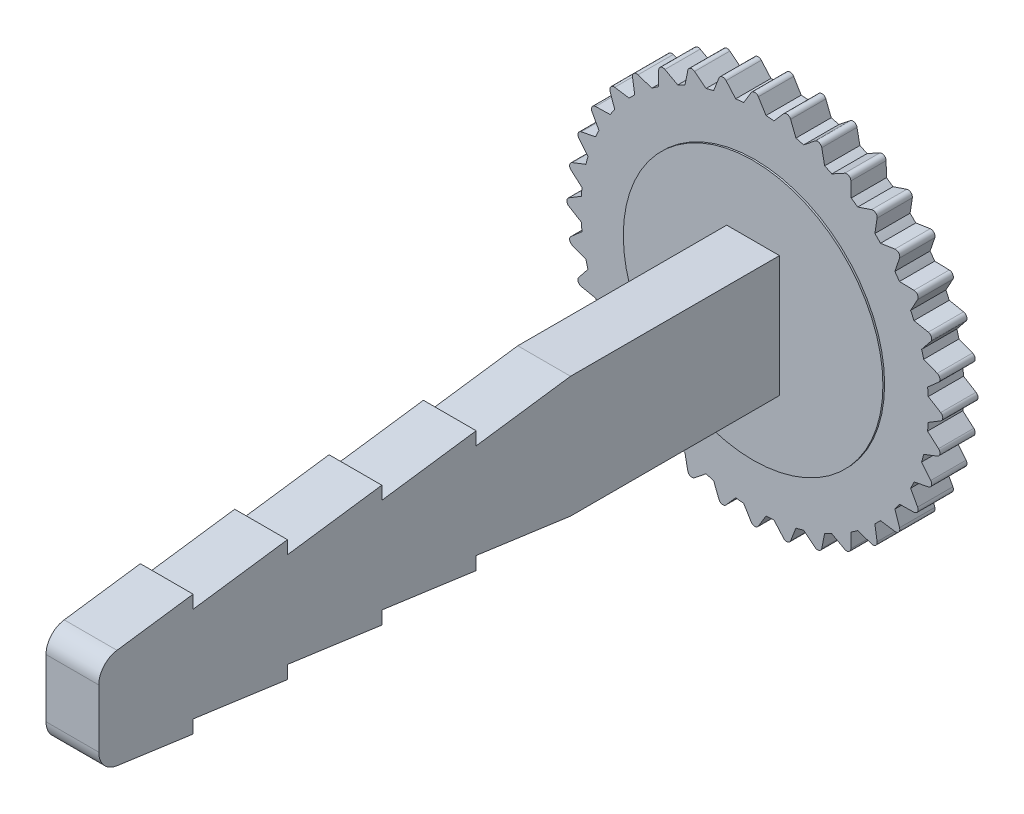
SolidWorks part; units mm, degrees
material "1060 Alloy"
ref_plane "Front Plane" through (0, 0, 0) normal (0, 0, 1) x (1, 0, 0)
ref_plane "Top Plane" through (0, 0, 0) normal (0, 1, 0) x (1, 0, 0)
ref_plane "Right Plane" through (0, 0, 0) normal (1, 0, 0) x (0, 0, -1)
sketch "Sketch1" plane through (0, 0, 0) normal (0, 0, 1) x (1, 0, 0)
  line L0 (0, 0) -> (0, 13.4429) construction
  line L1 (-0.53, 8.2179) -> (-0.1709, 8.8089)
  line L2 (0.53, 8.2179) -> (0.1709, 8.8089)
  line L5 (1.949, 8.001) -> (1.698, 8.6454)
  line L6 (0.9051, 8.1851) -> (1.3613, 8.7047)
  line L7 (3.3087, 7.5411) -> (3.1734, 8.2192)
  line L8 (2.3127, 7.9036) -> (2.8522, 8.3361)
  line L9 (4.568, 6.8519) -> (4.5524, 7.5432)
  line L10 (3.65, 7.3819) -> (4.2564, 7.7142)
  line L11 (5.6884, 5.9546) -> (5.7932, 6.6381)
  line L12 (4.8764, 6.636) -> (5.5313, 6.8578)
  line L13 (6.636, 4.8764) -> (6.8578, 5.5313)
  line L14 (5.9546, 5.6884) -> (6.6381, 5.7932)
  line L15 (7.3819, 3.65) -> (7.7142, 4.2564)
  line L16 (6.8519, 4.568) -> (7.5432, 4.5524)
  line L17 (7.9036, 2.3127) -> (8.3361, 2.8522)
  line L18 (7.5411, 3.3087) -> (8.2192, 3.1734)
  line L19 (8.1851, 0.9051) -> (8.7047, 1.3613)
  line L20 (8.001, 1.949) -> (8.6454, 1.698)
  line L21 (8.2179, -0.53) -> (8.8089, -0.1709)
  line L22 (8.2179, 0.53) -> (8.8089, 0.1709)
  line L23 (8.001, -1.949) -> (8.6454, -1.698)
  line L24 (8.1851, -0.9051) -> (8.7047, -1.3613)
  line L25 (7.5411, -3.3087) -> (8.2192, -3.1734)
  line L26 (7.9036, -2.3127) -> (8.3361, -2.8522)
  line L27 (6.8519, -4.568) -> (7.5432, -4.5524)
  line L28 (7.3819, -3.65) -> (7.7142, -4.2564)
  line L29 (5.9546, -5.6884) -> (6.6381, -5.7932)
  line L30 (6.636, -4.8764) -> (6.8578, -5.5313)
  line L31 (4.8764, -6.636) -> (5.5313, -6.8578)
  line L32 (5.6884, -5.9546) -> (5.7932, -6.6381)
  line L33 (3.65, -7.3819) -> (4.2564, -7.7142)
  line L34 (4.568, -6.8519) -> (4.5524, -7.5432)
  line L35 (2.3127, -7.9036) -> (2.8522, -8.3361)
  line L36 (3.3087, -7.5411) -> (3.1734, -8.2192)
  line L37 (0.9051, -8.1851) -> (1.3613, -8.7047)
  line L38 (1.949, -8.001) -> (1.698, -8.6454)
  line L39 (-0.53, -8.2179) -> (-0.1709, -8.8089)
  line L40 (0.53, -8.2179) -> (0.1709, -8.8089)
  line L41 (-1.949, -8.001) -> (-1.698, -8.6454)
  line L42 (-0.9051, -8.1851) -> (-1.3613, -8.7047)
  line L43 (-3.3087, -7.5411) -> (-3.1734, -8.2192)
  line L44 (-2.3127, -7.9036) -> (-2.8522, -8.3361)
  line L45 (-4.568, -6.8519) -> (-4.5524, -7.5432)
  line L46 (-3.65, -7.3819) -> (-4.2564, -7.7142)
  line L47 (-5.6884, -5.9546) -> (-5.7932, -6.6381)
  line L48 (-4.8764, -6.636) -> (-5.5313, -6.8578)
  line L49 (-6.636, -4.8764) -> (-6.8578, -5.5313)
  line L50 (-5.9546, -5.6884) -> (-6.6381, -5.7932)
  line L51 (-7.3819, -3.65) -> (-7.7142, -4.2564)
  line L52 (-6.8519, -4.568) -> (-7.5432, -4.5524)
  line L53 (-7.9036, -2.3127) -> (-8.3361, -2.8522)
  line L54 (-7.5411, -3.3087) -> (-8.2192, -3.1734)
  line L55 (-8.1851, -0.9051) -> (-8.7047, -1.3613)
  line L56 (-8.001, -1.949) -> (-8.6454, -1.698)
  line L57 (-8.2179, 0.53) -> (-8.8089, 0.1709)
  line L58 (-8.2179, -0.53) -> (-8.8089, -0.1709)
  line L59 (-8.001, 1.949) -> (-8.6454, 1.698)
  line L60 (-8.1851, 0.9051) -> (-8.7047, 1.3613)
  line L61 (-7.5411, 3.3087) -> (-8.2192, 3.1734)
  line L62 (-7.9036, 2.3127) -> (-8.3361, 2.8522)
  line L63 (-6.8519, 4.568) -> (-7.5432, 4.5524)
  line L64 (-7.3819, 3.65) -> (-7.7142, 4.2564)
  line L65 (-5.9546, 5.6884) -> (-6.6381, 5.7932)
  line L66 (-6.636, 4.8764) -> (-6.8578, 5.5313)
  line L67 (-4.8764, 6.636) -> (-5.5313, 6.8578)
  line L68 (-5.6884, 5.9546) -> (-5.7932, 6.6381)
  line L69 (-3.65, 7.3819) -> (-4.2564, 7.7142)
  line L70 (-4.568, 6.8519) -> (-4.5524, 7.5432)
  line L71 (-2.3127, 7.9036) -> (-2.8522, 8.3361)
  line L72 (-3.3087, 7.5411) -> (-3.1734, 8.2192)
  line L73 (-0.9051, 8.1851) -> (-1.3613, 8.7047)
  line L74 (-1.949, 8.001) -> (-1.698, 8.6454)
  arc A1 (-6.636, 4.8764) -> (-6.8519, 4.568) centre (0, 0) ccw
  arc A2 (0.1709, 8.8089) -> (-0.1709, 8.8089) centre (0, 8.705) ccw
  arc A3 (1.698, 8.6454) -> (1.3613, 8.7047) centre (1.5116, 8.5728) ccw
  arc A4 (3.1734, 8.2192) -> (2.8522, 8.3361) centre (2.9773, 8.18) ccw
  arc A5 (4.5524, 7.5432) -> (4.2564, 7.7142) centre (4.3525, 7.5388) ccw
  arc A6 (5.7932, 6.6381) -> (5.5313, 6.8578) centre (5.5955, 6.6684) ccw
  arc A7 (6.8578, 5.5313) -> (6.6381, 5.7932) centre (6.6684, 5.5955) ccw
  arc A8 (7.7142, 4.2564) -> (7.5432, 4.5524) centre (7.5388, 4.3525) ccw
  arc A9 (8.3361, 2.8522) -> (8.2192, 3.1734) centre (8.18, 2.9773) ccw
  arc A10 (8.7047, 1.3613) -> (8.6454, 1.698) centre (8.5728, 1.5116) ccw
  arc A11 (8.8089, -0.1709) -> (8.8089, 0.1709) centre (8.705, 0) ccw
  arc A12 (8.6454, -1.698) -> (8.7047, -1.3613) centre (8.5728, -1.5116) ccw
  arc A13 (8.2192, -3.1734) -> (8.3361, -2.8522) centre (8.18, -2.9773) ccw
  arc A14 (7.5432, -4.5524) -> (7.7142, -4.2564) centre (7.5388, -4.3525) ccw
  arc A15 (6.6381, -5.7932) -> (6.8578, -5.5313) centre (6.6684, -5.5955) ccw
  arc A16 (5.5313, -6.8578) -> (5.7932, -6.6381) centre (5.5955, -6.6684) ccw
  arc A17 (4.2564, -7.7142) -> (4.5524, -7.5432) centre (4.3525, -7.5388) ccw
  arc A18 (2.8522, -8.3361) -> (3.1734, -8.2192) centre (2.9773, -8.18) ccw
  arc A19 (1.3613, -8.7047) -> (1.698, -8.6454) centre (1.5116, -8.5728) ccw
  arc A20 (-0.1709, -8.8089) -> (0.1709, -8.8089) centre (0, -8.705) ccw
  arc A21 (-1.698, -8.6454) -> (-1.3613, -8.7047) centre (-1.5116, -8.5728) ccw
  arc A22 (-3.1734, -8.2192) -> (-2.8522, -8.3361) centre (-2.9773, -8.18) ccw
  arc A23 (-4.5524, -7.5432) -> (-4.2564, -7.7142) centre (-4.3525, -7.5388) ccw
  arc A24 (-5.7932, -6.6381) -> (-5.5313, -6.8578) centre (-5.5955, -6.6684) ccw
  arc A25 (-6.8578, -5.5313) -> (-6.6381, -5.7932) centre (-6.6684, -5.5955) ccw
  arc A26 (-7.7142, -4.2564) -> (-7.5432, -4.5524) centre (-7.5388, -4.3525) ccw
  arc A27 (-8.3361, -2.8522) -> (-8.2192, -3.1734) centre (-8.18, -2.9773) ccw
  arc A28 (-8.7047, -1.3613) -> (-8.6454, -1.698) centre (-8.5728, -1.5116) ccw
  arc A29 (-8.8089, 0.1709) -> (-8.8089, -0.1709) centre (-8.705, 0) ccw
  arc A30 (-8.6454, 1.698) -> (-8.7047, 1.3613) centre (-8.5728, 1.5116) ccw
  arc A31 (-8.2192, 3.1734) -> (-8.3361, 2.8522) centre (-8.18, 2.9773) ccw
  arc A32 (-7.5432, 4.5524) -> (-7.7142, 4.2564) centre (-7.5388, 4.3525) ccw
  arc A33 (-6.6381, 5.7932) -> (-6.8578, 5.5313) centre (-6.6684, 5.5955) ccw
  arc A34 (-5.5313, 6.8578) -> (-5.7932, 6.6381) centre (-5.5955, 6.6684) ccw
  arc A35 (-4.2564, 7.7142) -> (-4.5524, 7.5432) centre (-4.3525, 7.5388) ccw
  arc A36 (-2.8522, 8.3361) -> (-3.1734, 8.2192) centre (-2.9773, 8.18) ccw
  arc A37 (-1.3613, 8.7047) -> (-1.698, 8.6454) centre (-1.5116, 8.5728) ccw
  arc A38 (-5.6884, 5.9546) -> (-5.9546, 5.6884) centre (0, 0) ccw
  arc A39 (-4.568, 6.8519) -> (-4.8764, 6.636) centre (0, 0) ccw
  arc A40 (-3.3087, 7.5411) -> (-3.65, 7.3819) centre (0, 0) ccw
  arc A41 (-1.949, 8.001) -> (-2.3127, 7.9036) centre (0, 0) ccw
  arc A42 (-0.53, 8.2179) -> (-0.9051, 8.1851) centre (0, 0) ccw
  arc A43 (0.9051, 8.1851) -> (0.53, 8.2179) centre (0, 0) ccw
  arc A44 (2.3127, 7.9036) -> (1.949, 8.001) centre (0, 0) ccw
  arc A45 (3.65, 7.3819) -> (3.3087, 7.5411) centre (0, 0) ccw
  arc A46 (4.8764, 6.636) -> (4.568, 6.8519) centre (0, 0) ccw
  arc A47 (6.8519, 4.568) -> (6.636, 4.8764) centre (0, 0) ccw
  arc A48 (5.9546, 5.6884) -> (5.6884, 5.9546) centre (0, 0) ccw
  arc A49 (7.5411, 3.3087) -> (7.3819, 3.65) centre (0, 0) ccw
  arc A50 (8.001, 1.949) -> (7.9036, 2.3127) centre (0, 0) ccw
  arc A51 (8.2179, 0.53) -> (8.1851, 0.9051) centre (0, 0) ccw
  arc A52 (8.1851, -0.9051) -> (8.2179, -0.53) centre (0, 0) ccw
  arc A53 (7.9036, -2.3127) -> (8.001, -1.949) centre (0, 0) ccw
  arc A54 (7.3819, -3.65) -> (7.5411, -3.3087) centre (0, 0) ccw
  arc A55 (6.636, -4.8764) -> (6.8519, -4.568) centre (0, 0) ccw
  arc A56 (5.6884, -5.9546) -> (5.9546, -5.6884) centre (0, 0) ccw
  arc A57 (4.568, -6.8519) -> (4.8764, -6.636) centre (0, 0) ccw
  arc A58 (3.3087, -7.5411) -> (3.65, -7.3819) centre (0, 0) ccw
  arc A59 (1.949, -8.001) -> (2.3127, -7.9036) centre (0, 0) ccw
  arc A60 (0.53, -8.2179) -> (0.9051, -8.1851) centre (0, 0) ccw
  arc A61 (-0.9051, -8.1851) -> (-0.53, -8.2179) centre (0, 0) ccw
  arc A62 (-2.3127, -7.9036) -> (-1.949, -8.001) centre (0, 0) ccw
  arc A63 (-3.65, -7.3819) -> (-3.3087, -7.5411) centre (0, 0) ccw
  arc A64 (-4.8764, -6.636) -> (-4.568, -6.8519) centre (0, 0) ccw
  arc A65 (-5.9546, -5.6884) -> (-5.6884, -5.9546) centre (0, 0) ccw
  arc A66 (-6.8519, -4.568) -> (-6.636, -4.8764) centre (0, 0) ccw
  arc A67 (-7.5411, -3.3087) -> (-7.3819, -3.65) centre (0, 0) ccw
  arc A68 (-8.001, -1.949) -> (-7.9036, -2.3127) centre (0, 0) ccw
  arc A69 (-8.2179, -0.53) -> (-8.1851, -0.9051) centre (0, 0) ccw
  arc A70 (-7.3819, 3.65) -> (-7.5411, 3.3087) centre (0, 0) ccw
  arc A71 (-7.9036, 2.3127) -> (-8.001, 1.949) centre (0, 0) ccw
  arc A72 (-8.1851, 0.9051) -> (-8.2179, 0.53) centre (0, 0) ccw
  point P190 (0, 0)
  dimension "D2" = 16.47
  dimension "D5" = 0.2
  dimension "D3" = 1.06
  dimension "D4" = 1.06
  dimension "D6" = 36
extrude "Boss-Extrude1" add sketch "Sketch1" along normal blind 1.67
sketch "Sketch2" plane through (0, 0, 1.67) normal (0, 0, 1) x (1, 0, 0)
  line L1 (-1.25, 2.87) -> (1.25, 2.87)
  line L2 (-1.25, 2.87) -> (-1.25, -2.87)
  line L3 (-1.25, -2.87) -> (1.25, -2.87)
  line L4 (1.25, 2.87) -> (1.25, -2.87)
  point P4 (-1.25, 0)
  point P6 (0, -2.87)
  dimension "D1" = 2.5
  dimension "D2" = 5.74
extrude "Boss-Extrude8" add sketch "Sketch2" along normal offset from surface (32.33 mm away) 34 up to face at (0, 0, 0)
sketch "Sketch3" plane through (1.25, 0, 0) normal (1, 0, 0) x (0, 0, -1)
  line L0 (-1.67, 2.87) -> (-11.65, 2.87)
  line L1 (-34, 2.87) -> (-1.67, 2.87) construction
  line L2 (-11.65, 2.87) -> (-16.12, 2.25)
  line L3 (-16.12, 2.25) -> (-16.12, 2.87)
  line L4 (-16.12, 2.87) -> (-20.59, 2.25)
  line L5 (-1.67, 0) -> (-34, 0) construction
  line L6 (-1.67, -2.87) -> (-1.67, 2.87) construction
  line L7 (-34, -2.87) -> (-34, 2.87) construction
  line L8 (-29.53, -2.87) -> (-34, -2.25)
  line L9 (-29.53, -2.25) -> (-29.53, -2.87)
  line L10 (-25.06, -2.87) -> (-29.53, -2.25)
  line L11 (-20.59, 2.25) -> (-20.59, 2.87)
  line L12 (-20.59, 2.87) -> (-25.06, 2.25)
  line L13 (-25.06, 2.25) -> (-25.06, 2.87)
  line L14 (-25.06, 2.87) -> (-29.53, 2.25)
  line L15 (-29.53, 2.25) -> (-29.53, 2.87)
  line L16 (-29.53, 2.87) -> (-34, 2.25)
  line L17 (-34, 2.25) -> (-34, -2.25)
  line L18 (-25.06, -2.25) -> (-25.06, -2.87)
  line L19 (-20.59, -2.87) -> (-25.06, -2.25)
  line L20 (-20.59, -2.25) -> (-20.59, -2.87)
  line L21 (-16.12, -2.87) -> (-20.59, -2.25)
  line L22 (-16.12, -2.25) -> (-16.12, -2.87)
  line L23 (-11.65, -2.87) -> (-16.12, -2.25)
  line L24 (-1.67, -2.87) -> (-11.65, -2.87)
  line L25 (-34, 2.25) -> (-34, 2.87)
  line L26 (-34, 2.87) -> (-11.65, 2.87)
  line L27 (-34, -2.25) -> (-34, -2.87)
  line L28 (-34, -2.87) -> (-11.65, -2.87)
  line M24 (-34, 2.87) -> (-34, -2.87)
  line M25 (-34, -2.87) -> (-1.67, -2.87)
  line M27 (-1.67, 2.87) -> (-34, 2.87)
  dimension "D2" = 4.47
  dimension "D3" = 4.47
  dimension "D5" = 4.47
  dimension "D6" = 4.47
  dimension "D7" = 4.47
extrude "Cut-Extrude1" cut sketch "Sketch3" against normal blind 34 contours L8 M25 M24 | L10 L9 M25 | L19 L18 M25 | L21 L20 M25 | L23 L22 M25 | L3 L2 M27 | L11 L4 M27 | L13 L12 M27 | L15 L14 M27 | L16 M27 M24 region at (1.25, -2.6633, 14.63) region at (1.25, -2.6633, 19.1) region at (1.25, -2.6633, 23.57) region at (1.25, -2.6633, 28.04) region at (1.25, -2.6633, 32.51) region at (1.25, 2.6633, 32.51) region at (1.25, 2.6633, 28.04) region at (1.25, 2.6633, 23.57) region at (1.25, 2.6633, 19.1) region at (1.25, 2.6633, 14.63)
fillet "Fillet1" radius 1 2 edges at (0, 2.25, 34) (0, -2.25, 34)
sketch "Sketch4" plane through (0, 0, 0) normal (0, 0, -1) x (-1, 0, 0)
  circle A0 centre (0, 0) radius 6.15
  dimension "D1" = 12.3
extrude "Cut-Extrude2" cut sketch "Sketch4" against normal blind 0.08
sketch "Sketch5" plane through (0, 0, 1.67) normal (0, 0, 1) x (1, 0, 0)
  circle A0 centre (0, 0) radius 6.15
  dimension "D1" = 12.3
extrude "Boss-Extrude9" add sketch "Sketch5" along normal blind 0.08
sketch "Sketch6" plane through (0, 0, 0.08) normal (0, 0, -1) x (-1, 0, 0)
  circle A0 centre (0, 0) radius 2.5
  dimension "D1" = 5
extrude "Boss-Extrude10" add sketch "Sketch6" along normal blind 0.19
